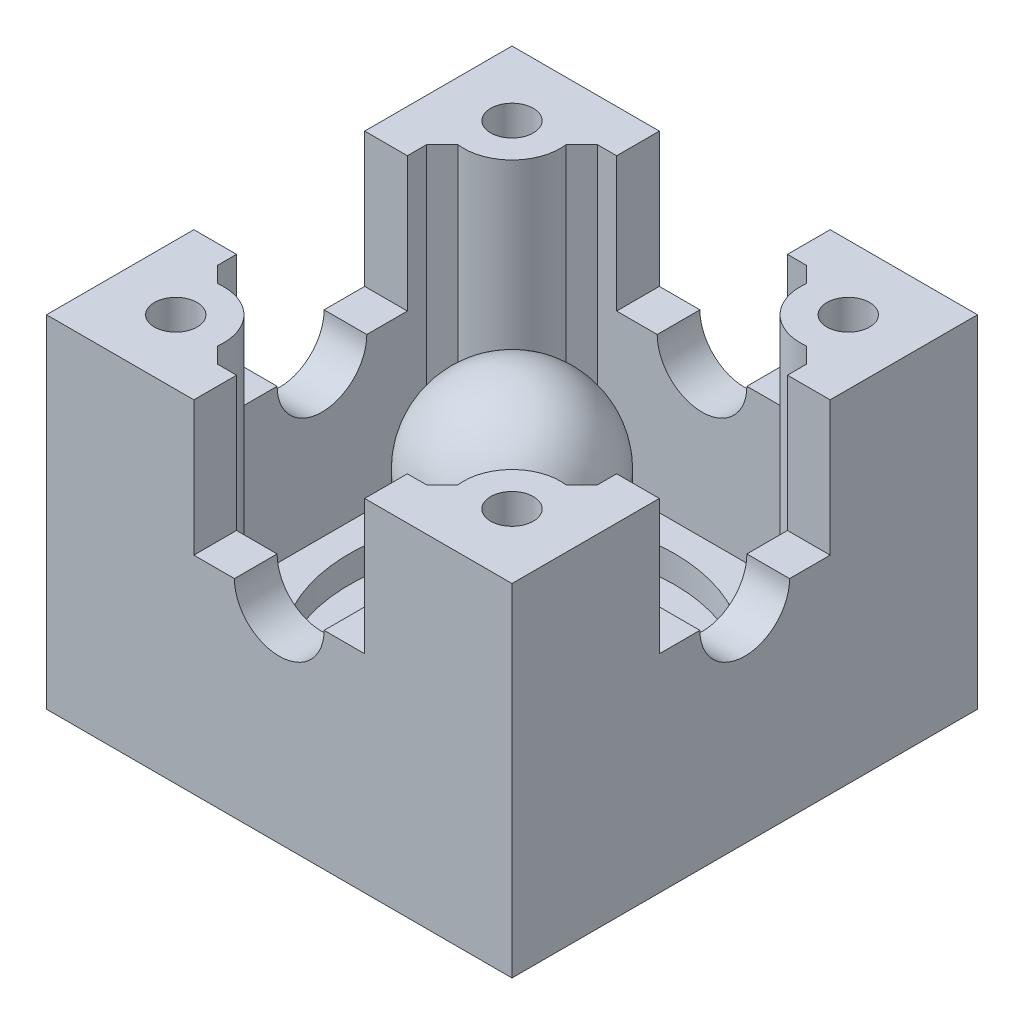
SolidWorks part; units mm, degrees
ref_plane "Front Plane" through (0, 0, 0) normal (0, 0, 1) x (1, 0, 0)
ref_plane "Top Plane" through (0, 0, 0) normal (0, 1, 0) x (1, 0, 0)
ref_plane "Right Plane" through (0, 0, 0) normal (1, 0, 0) x (0, 0, -1)
sketch "Sketch1" plane through (0, 0, 0) normal (0, 1, 0) x (1, 0, 0)
  line L1 (0, 0) -> (13.843, 0)
  line L2 (0, 0) -> (0, 13.843)
  line L3 (0, 13.843) -> (13.843, 13.843)
  line L4 (13.843, 0) -> (13.843, 13.843)
  dimension "D1" = 13.843
  dimension "D2" = 13.843
extrude "main body extrude" add sketch "Sketch1" along normal blind 10.16
sketch "Sketch4" plane through (0, 10.16, 0) normal (0, 1, 0) x (1, 0, 0)
  line L0 (0, 13.843) -> (13.843, 0) construction
  line L1 (13.843, 0) -> (13.843, 13.843) construction
  line L2 (1.27, 10.033) -> (3.81, 12.573)
  line L7 (13.843, 13.843) -> (0, 13.843) construction
  line L8 (3.81, 1.27) -> (10.033, 1.27)
  line L9 (10.033, 12.573) -> (12.573, 10.033)
  line L10 (0, 0) -> (13.843, 0) construction
  line L15 (1.27, 3.81) -> (1.27, 10.033)
  line L16 (3.81, 12.573) -> (10.033, 12.573)
  line L17 (12.573, 3.81) -> (12.573, 10.033)
  line L18 (1.27, 1.27) -> (12.573, 12.573) construction
  line L19 (1.27, 12.573) -> (12.573, 1.27) construction
  line L20 (10.033, 1.27) -> (12.573, 3.81)
  line L21 (1.27, 3.81) -> (3.81, 1.27)
  circle A0 centre (1.9215, 11.9215) radius 0.635
  circle A1 centre (11.9215, 11.9215) radius 0.635
  circle A2 centre (11.9215, 1.9215) radius 0.635
  circle A3 centre (1.9215, 1.9215) radius 0.635
  circle A4 centre (1.9215, 11.9215) radius 1.435
  circle A5 centre (11.9215, 11.9215) radius 1.435
  circle A6 centre (11.9215, 1.9215) radius 1.435
  circle A7 centre (1.9215, 1.9215) radius 1.435
  point P5 (6.9215, 6.9215)
  point P6 (6.9215, 6.9215)
  point P27 (6.9215, 6.9215)
  point P28 (6.9215, 6.9215)
  point P44 (6.9215, 6.9215)
  dimension "D3" = 1.27
  dimension "D6" = 0.8
  dimension "D1" = 1.27
  dimension "D2" = 1.27
  dimension "D5" = 10
  dimension "D4" = 4
  dimension "D7" = 4
extrude "main body cut" cut sketch "Sketch4" against normal offset from surface (9.36 mm away) 0.8 contours L8 region at (6.9215, 10.16, -6.9215) up to face at (6.9215, 0, -6.9215)
sketch "Sketch21" plane through (0, 10.16, 0) normal (0, 1, 0) x (1, 0, 0)
  line L0 (0, 13.843) -> (13.843, 0) construction
  circle A0 centre (1.9215, 11.9215) radius 0.635
  circle A1 centre (11.9215, 11.9215) radius 0.635
  circle A2 centre (11.9215, 1.9215) radius 0.635
  circle A3 centre (1.9215, 1.9215) radius 0.635
  point P7 (6.9215, 6.9215)
  point P17 (6.9215, 6.9215)
  dimension "D2" = 1.27
  dimension "D1" = 4
extrude "screw holes cut" cut sketch "Sketch21" against normal through all
sketch "Sketch5" plane through (0, 0, 0) normal (0, 0, 1) x (1, 0, 0)
  line L0 (6.9215, 12.7116) -> (6.9215, 6.1595) construction
  line L1 (8.255, 12.7116) -> (8.255, 6.1595)
  line L2 (0, 10.16) -> (13.843, 10.16) construction
  line L3 (5.588, 12.7116) -> (5.588, 6.1595)
  line L4 (6.9215, 6.1595) -> (6.9215, 2.6781) construction
  line L5 (4.3815, 12.7116) -> (9.4615, 12.7116)
  line L6 (4.3815, 12.7116) -> (4.3815, 6.1595)
  line L7 (4.3815, 6.1595) -> (9.4615, 6.1595)
  line L8 (9.4615, 12.7116) -> (9.4615, 6.1595)
  line L9 (4.3815, 12.7116) -> (9.4615, 6.1595) construction
  line L10 (4.3815, 6.1595) -> (9.4615, 12.7116) construction
  line L19 (11.811, 5.207) -> (10.541, 5.207)
  line L20 (2.032, 8.509) -> (3.302, 8.509)
  line L21 (2.032, 8.509) -> (2.032, 5.207)
  line L22 (2.032, 5.207) -> (3.302, 5.207)
  line L23 (3.302, 8.509) -> (3.302, 5.207)
  line L24 (10.541, 8.509) -> (10.541, 5.207)
  line L25 (11.811, 8.509) -> (10.541, 8.509)
  line L26 (11.811, 8.509) -> (11.811, 5.207)
  arc A1 (8.255, 12.7116) -> (5.588, 12.7116) centre (6.9215, 12.7116) ccw
  arc A2 (5.588, 6.1595) -> (8.255, 6.1595) centre (6.9215, 6.1595) ccw
  circle A3 centre (6.9215, 6.1595) radius 1.3335 construction
  point P2 (6.9215, 10.16)
  point P3 (6.9215, 9.4356)
  point P14 (6.9215, 9.4356)
  line M8 (13.843, 10.16) -> (0, 10.16)
  dimension "D1" = 2.667
  dimension "D2" = 4.0005
  dimension "D3" = 5.08
  dimension "D4" = 1.27
  dimension "D5" = 3.302
  dimension "D6" = 7.239
  dimension "D7" = 1.651
extrude "x axis slot" cut sketch "Sketch5" against normal through all contours L6 L7 L3 M8 | L3 L7 L1 M8 | L8 L1 L7 M8 | L7 A2 region at (8.8583, 8.1598, 0) region at (6.9215, 8.1598, 0) region at (6.9215, 5.5935, 0) region at (4.9848, 8.1598, 0)
sketch "Sketch6" plane through (13.843, 0, 0) normal (1, 0, 0) x (0, 0, -1)
  line L0 (0, 10.16) -> (13.843, 10.16) construction
  line L1 (6.9215, 6.1595) -> (6.9215, 12.6452) construction
  line L2 (5.588, 6.1595) -> (5.588, 12.6452)
  line L3 (8.255, 6.1595) -> (8.255, 12.6452)
  line L4 (6.9215, 6.1595) -> (6.9215, 2.9038) construction
  line L5 (4.3815, 12.6452) -> (9.4615, 12.6452)
  line L6 (4.3815, 12.6452) -> (4.3815, 6.1595)
  line L7 (4.3815, 6.1595) -> (9.4615, 6.1595)
  line L8 (9.4615, 12.6452) -> (9.4615, 6.1595)
  line L9 (4.3815, 12.6452) -> (9.4615, 6.1595) construction
  line L10 (4.3815, 6.1595) -> (9.4615, 12.6452) construction
  circle A0 centre (6.9215, 6.1595) radius 1.3335 construction
  arc A1 (5.588, 6.1595) -> (8.255, 6.1595) centre (6.9215, 6.1595) ccw
  arc A2 (8.255, 12.6452) -> (5.588, 12.6452) centre (6.9215, 12.6452) ccw
  point P6 (6.9215, 10.16)
  point P7 (6.9215, 9.4024)
  point P13 (6.9215, 7.493)
  point P15 (6.9215, 9.4024)
  line M8 (13.843, 10.16) -> (0, 10.16)
  dimension "D1" = 2.667
  dimension "D2" = 4.0005
  dimension "D3" = 5.08
extrude "y axis slot" cut sketch "Sketch6" against normal through all contours L6 L7 L2 M8 | L2 L7 L3 M8 | L7 A1 | L8 L3 L7 M8 region at (13.843, 8.1598, -4.9848) region at (13.843, 8.1598, -6.9215) region at (13.843, 5.5935, -6.9215) region at (13.843, 8.1598, -8.8582)
sketch "Sketch11" plane through (0, 0.8, 0) normal (0, 1, 0) x (1, 0, 0)
  line L0 (1.27, 12.573) -> (12.573, 1.27) construction
  line L1 (12.573, 12.573) -> (1.27, 1.27) construction
  line L3 (1.27, 12.573) -> (12.573, 12.573)
  line L4 (1.27, 12.573) -> (1.27, 1.27)
  line L5 (1.27, 1.27) -> (12.573, 1.27)
  line L6 (12.573, 12.573) -> (12.573, 1.27)
  line L9 (3.81, 12.573) -> (4.3815, 12.573) construction
  line L10 (1.27, 9.4615) -> (1.27, 10.033) construction
  line L12 (3.81, 1.27) -> (4.3815, 1.27) construction
  circle A0 centre (6.9215, 6.9215) radius 4.826
  circle A1 centre (1.9215, 11.9215) radius 0.635
  circle A2 centre (11.9215, 11.9215) radius 0.635
  circle A3 centre (11.9215, 1.9215) radius 0.635
  circle A4 centre (1.9215, 1.9215) radius 0.635
  dimension "D1" = 9.652
extrude "spring retainer extrude" add sketch "Sketch11" along normal blind 0.8
sketch "Sketch12" plane through (0, 0.8, 0) normal (0, 1, 0) x (1, 0, 0)
  line L0 (0, 13.843) -> (13.843, 0) construction
  circle A0 centre (6.9215, 6.9215) radius 2.54
  dimension "D1" = 5.08
extrude "Stick support" add sketch "Sketch12" along normal up to vertex (5.3595 mm away) up to point (5.588, 6.1595, -1.27)
sketch "Sketch20" plane through (0, 6.1595, 0) normal (0, 1, 0) x (1, 0, 0)
  circle A0 centre (6.9215, 6.9215) radius 2.54
  circle A1 centre (6.9215, 6.9215) radius 2.54 construction
extrude "Boss-Extrude9" add sketch "Sketch20" along normal blind 2.54
fillet "Fillet4" radius 2.54 1 edges at (6.9215, 8.6995, -4.3815)
sketch "Sketch16" [suppressed] plane through (0, 10.16, 0) normal (0, 1, 0) x (1, 0, 0)
  line L0 (1.2, 10.103) -> (3.74, 12.643)
  line L1 (1.2, 12.643) -> (1.2, 1.2) construction
  line L2 (12.643, 12.643) -> (1.2, 12.643) construction
  line L3 (1.2, 10.103) -> (1.2, 12.643)
  line L4 (1.2, 12.643) -> (3.74, 12.643)
  line L5 (0, 13.843) -> (13.843, 0) construction
  line L6 (10.103, 12.643) -> (12.643, 10.103)
  line L7 (12.643, 12.643) -> (12.643, 10.103)
  line L8 (10.103, 12.643) -> (12.643, 12.643)
  line L9 (12.643, 3.74) -> (10.103, 1.2)
  line L10 (12.643, 1.2) -> (10.103, 1.2)
  line L11 (12.643, 3.74) -> (12.643, 1.2)
  line L12 (3.74, 1.2) -> (1.2, 3.74)
  line L13 (1.2, 1.2) -> (1.2, 3.74)
  line L14 (3.74, 1.2) -> (1.2, 1.2)
  point P12 (6.9215, 6.9215)
  point P25 (6.9215, 6.9215)
  dimension "D1" = 2.54
  dimension "D2" = 2.54
  dimension "D3" = 4
extrude "screw extrude 1" [suppressed] add sketch "Sketch16" against normal up to surface (8.56 mm away) up to face at (6.9215, 1.6, -2.0955)
sketch "Sketch15" [suppressed] plane through (0, 10.16, 0) normal (0, 1, 0) x (1, 0, 0)
  line L0 (0, 13.843) -> (13.843, 0) construction
  circle A0 centre (1.9215, 11.9215) radius 0.635
  circle A1 centre (11.9215, 11.9215) radius 0.635
  circle A2 centre (11.9215, 1.9215) radius 0.635
  circle A3 centre (1.9215, 1.9215) radius 0.635
  point P4 (6.9215, 6.9215)
  point P16 (6.9215, 6.9215)
  dimension "D1" = 1.27
  dimension "D3" = 10
  dimension "D2" = 4
extrude "screw cut 2" [suppressed] cut sketch "Sketch15" against normal through all
sketch "Sketch17" [suppressed] plane through (0, 10.16, 0) normal (0, 1, 0) x (1, 0, 0)
  line L0 (0, 13.843) -> (13.843, 0) construction
  circle A0 centre (1.9215, 11.9215) radius 1.143
  circle A1 centre (11.9215, 11.9215) radius 1.143
  circle A2 centre (11.9215, 1.9215) radius 1.143
  circle A3 centre (1.9215, 1.9215) radius 1.143
  circle A4 centre (1.9215, 11.9215) radius 0.635 construction
  circle A5 centre (1.9215, 11.9215) radius 0.635
  circle A6 centre (11.9215, 11.9215) radius 0.635
  circle A7 centre (11.9215, 1.9215) radius 0.635
  circle A8 centre (1.9215, 1.9215) radius 0.635
  point P7 (6.9215, 6.9215)
  point P17 (6.9215, 6.9215)
  point P27 (6.9215, 6.9215)
  dimension "D2" = 0.508
  dimension "D1" = 4
  dimension "D3" = 4
extrude "screw extrude 2" [suppressed] add sketch "Sketch17" against normal up to surface (8.56 mm away) up to face at (6.9215, 1.6, -2.0955)
sketch "Sketch9" plane through (0, 0, 0) normal (0, -1, 0) x (1, 0, 0)
  line L0 (6.9215, 0) -> (6.9215, -13.843) construction
  line L1 (0, 0) -> (13.843, 0) construction
  line L2 (13.843, -13.843) -> (0, -13.843) construction
  line L3 (0, -6.9215) -> (13.843, -6.9215) construction
  line L4 (0, -13.843) -> (0, 0) construction
  line L5 (13.843, 0) -> (13.843, -13.843) construction
  circle A0 centre (6.9215, -1.8415) radius 0.625
  circle A1 centre (6.9215, -12.0015) radius 0.625
  dimension "D1" = 1.25
  dimension "D2" = 10.16
extrude "mounting holes 1 cut " [suppressed] cut sketch "Sketch9" against normal blind 2.54
chamfer "Chamfer1" [suppressed] distance 0.635 angle 45
